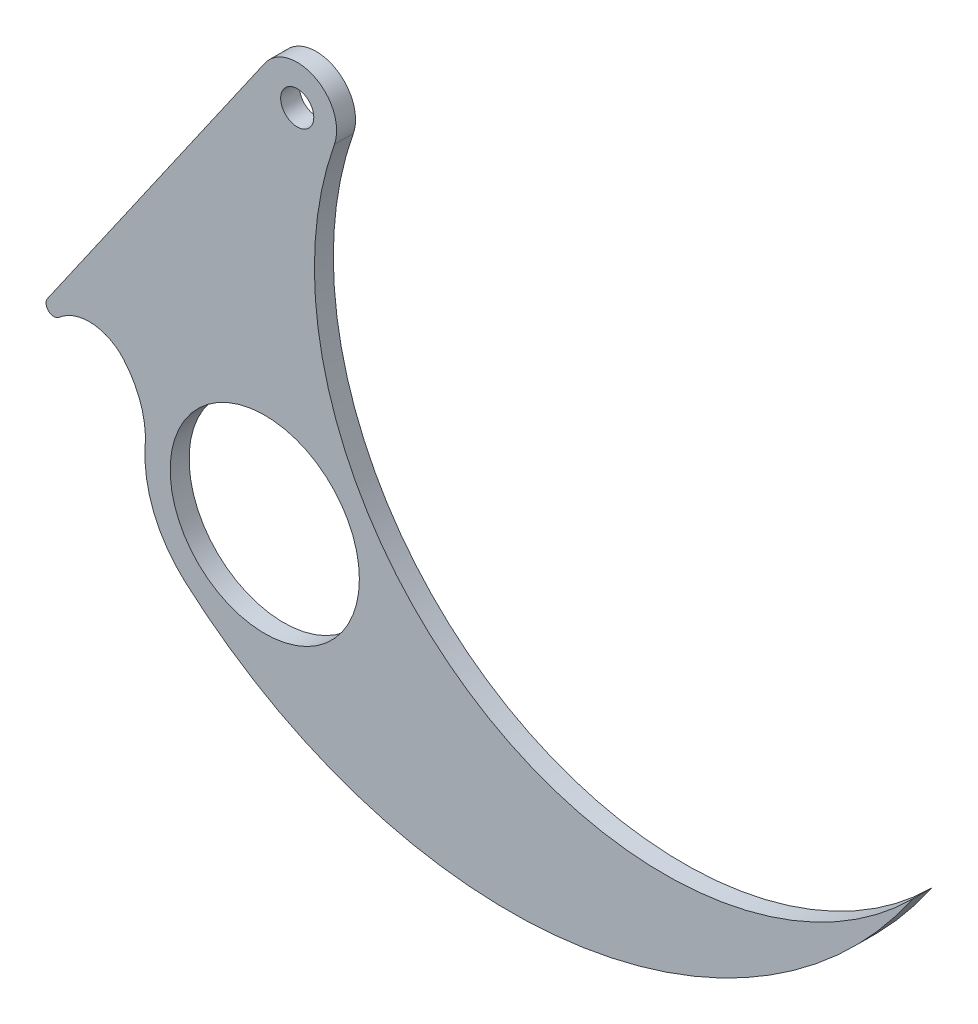
SolidWorks part; units mm, degrees
material "AISI 1020"
ref_plane "Спереди" through (0, 0, 0) normal (0, 0, 1) x (1, 0, 0)
ref_plane "Сверху" through (0, 0, 0) normal (0, 1, 0) x (1, 0, 0)
ref_plane "Справа" through (0, 0, 0) normal (1, 0, 0) x (0, 0, -1)
sketch "Эскиз1" plane through (0, 0, 0) normal (0, 0, 1) x (1, 0, 0)
  line L0 (0.0334, 126.6948) -> (-68.9133, 27.5625)
  line L1 (-66.8609, 26.135) -> (-55.6519, 13.3539) construction
  line L2 (-55.6519, 13.3539) -> (-44.7503, 22.9145) construction
  circle A0 centre (10.2955, 119.5575) radius 5.25 construction
  circle A1 centre (10.2955, 119.5575) radius 12.5 construction
  circle A2 centre (0, 0) radius 30 construction
  circle A3 centre (0, 0) radius 38 construction
  arc A4 (-25.219, -28.4254) -> (205.5746, 0) centre (77.648, 87.5202) ccw construction
  arc A5 (22.0814, 115.3933) -> (205.5746, 0) centre (126.8361, 78.3816) ccw construction
  circle A6 centre (10.2955, 119.5575) radius 5.25
  arc A7 (22.0814, 115.3933) -> (0.0334, 126.6948) centre (10.2955, 119.5575) ccw
  circle A8 centre (0, 0) radius 30
  arc A9 (-37.9088, 2.6317) -> (-25.219, -28.4254) centre (0, 0) ccw
  arc A10 (-25.219, -28.4254) -> (205.5746, 0) centre (77.648, 87.5202) ccw
  arc A11 (22.0814, 115.3933) -> (205.5746, 0) centre (126.8361, 78.3816) ccw
  arc A13 (-68.9133, 27.5625) -> (-65.2125, 24.2554) centre (-66.8609, 26.135) ccw
  circle A14 centre (-55.6519, 13.3539) radius 14.5 construction
  arc A15 (-44.7503, 22.9145) -> (-65.2125, 24.2554) centre (-55.6519, 13.3539) ccw
  arc A16 (-44.7503, 22.9145) -> (-37.9088, 2.6317) centre (-65.6795, 4.5597) cw
  dimension "D1" = 5
  dimension "D2" = 19
base flange "Базовая кромка1" sketch "Эскиз1" thickness 6 reverse thickness direction no parameters "D1"=0.74
sketch "Сгиб-Линии1" [suppressed] plane through (0, 0, 0) normal (0, 1, 0) x (1, 0, 0)
sketch "Граничная рамка1" [suppressed] plane through (0, 0, 0) normal (0, 1, 0) x (1, 0, 0)
sheet metal parameters "Листовой металл3" thickness 6 parameters "D1"=0.74
flat pattern "Развертка3" [suppressed]
sketch "Сгиб-Линии2" plane through (0, 0, 0) normal (0, 1, 0) x (1, 0, 0)
sketch3d "Граничная рамка2" [suppressed]
  line L0 (-70.887, 49.6912, 0) -> (127.9276, -87.521, 0) construction
  line L1 (-159.2877, -78.3977, 0) -> (39.5269, -215.6099, 0) construction
  line L2 (-70.887, 49.6912, 0) -> (-159.2877, -78.3977, 0) construction
  line L3 (127.9276, -87.521, 0) -> (39.5269, -215.6099, 0) construction
